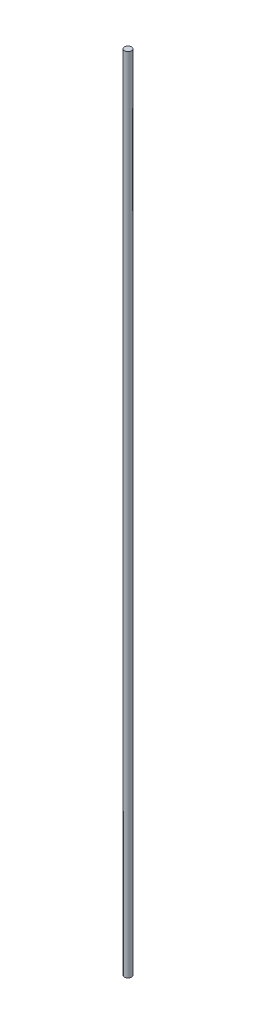
SolidWorks part; units mm, degrees
material "AISI 1020"
ref_plane "Front Plane" through (0, 0, 0) normal (0, 0, 1) x (1, 0, 0)
ref_plane "Top Plane" through (0, 0, 0) normal (0, 1, 0) x (1, 0, 0)
ref_plane "Right Plane" through (0, 0, 0) normal (1, 0, 0) x (0, 0, -1)
sketch "Threaded Rod Profile" plane through (0, 0, 0) normal (0, 1, 0) x (1, 0, 0)
  circle A0 centre (0, 0) radius 3.175
  dimension "D1" = 6.35
extrude "Threaded Rod Body" add sketch "Threaded Rod Profile" along normal blind 730.25
equation "\"Diameter\"= 0.25"
equation "\"Length\"=28.75"
equation "\"D1@Threaded Rod Profile\" = \"Diameter\""
equation "\"D1@Threaded Rod Body\" = \"Length\""
